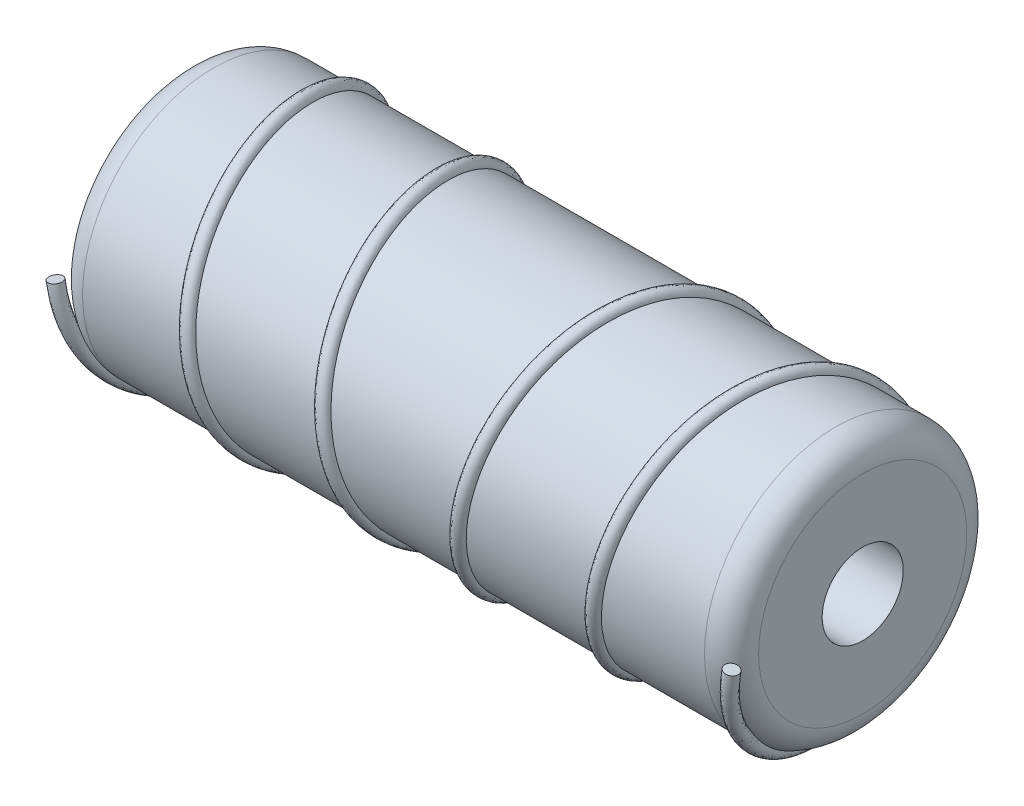
SolidWorks part; units mm, degrees
material "Borracha de silicone"
ref_plane "Plano frontal" through (0, 0, 0) normal (0, 0, 1) x (1, 0, 0)
ref_plane "Plano superior" through (0, 0, 0) normal (0, 1, 0) x (1, 0, 0)
ref_plane "Plano direito" through (0, 0, 0) normal (1, 0, 0) x (0, 0, -1)
sketch "Esboço1" plane through (0, 0, 0) normal (0, 0, 1) x (1, 0, 0)
  line L0 (0, 0) -> (50, 0) construction
  line L1 (0, 0) -> (0, 9.7)
  line L2 (50, 9.7) -> (0, 9.7)
  line L4 (50, 9.7) -> (50, 0)
  line L5 (25, 0) -> (25, 5.8) construction
  line L6 (0, 0) -> (50, 0)
  dimension "D1" = 50
  dimension "D2" = 5.8
  dimension "D3" = 9.7
revolve "Revolução1" add sketch "Esboço1" angle 360 about L6
fillet "Filete2" radius 2 2 edges at (50, 0, 9.7) (0, 0, 9.7)
sketch "Esboço2" plane through (0, 0, 0) normal (-1, 0, 0) x (0, 0, 1)
  circle A0 centre (0, 0) radius 3
  dimension "D1" = 6
extrude "Corte-extrusão1" cut sketch "Esboço2" against normal through all
sketch "Esboço4" plane through (50, 0, 0) normal (1, 0, 0) x (0, 0, -1)
  circle A0 centre (0, 0) radius 9.7
  circle A1 centre (0, 0) radius 9.7 construction
curve "Hélice/Espiral1" pitch 10 height 25 radius 9.7 left hand yes centre (50, 0, 0) axis (-1, 0, 0) start towards (0, 0, 1)
sweep "Varredura1" add path "Hélice/Espiral1" circular profile diameter 1 parameters "D3"=1
sketch "Esboço18" plane through (0, 0, 0) normal (-1, 0, 0) x (0, 0, 1)
  circle A0 centre (0, 0) radius 9.7
  circle A1 centre (0, 0) radius 9.7 construction
curve "Hélice/Espiral2" pitch 10 height 25 radius 9.7 centre (0, 0, 0) axis (1, 0, 0) start towards (0, 0, 1)
sweep "Varredura2" add path "Hélice/Espiral2" circular profile diameter 1 parameters "D3"=1
